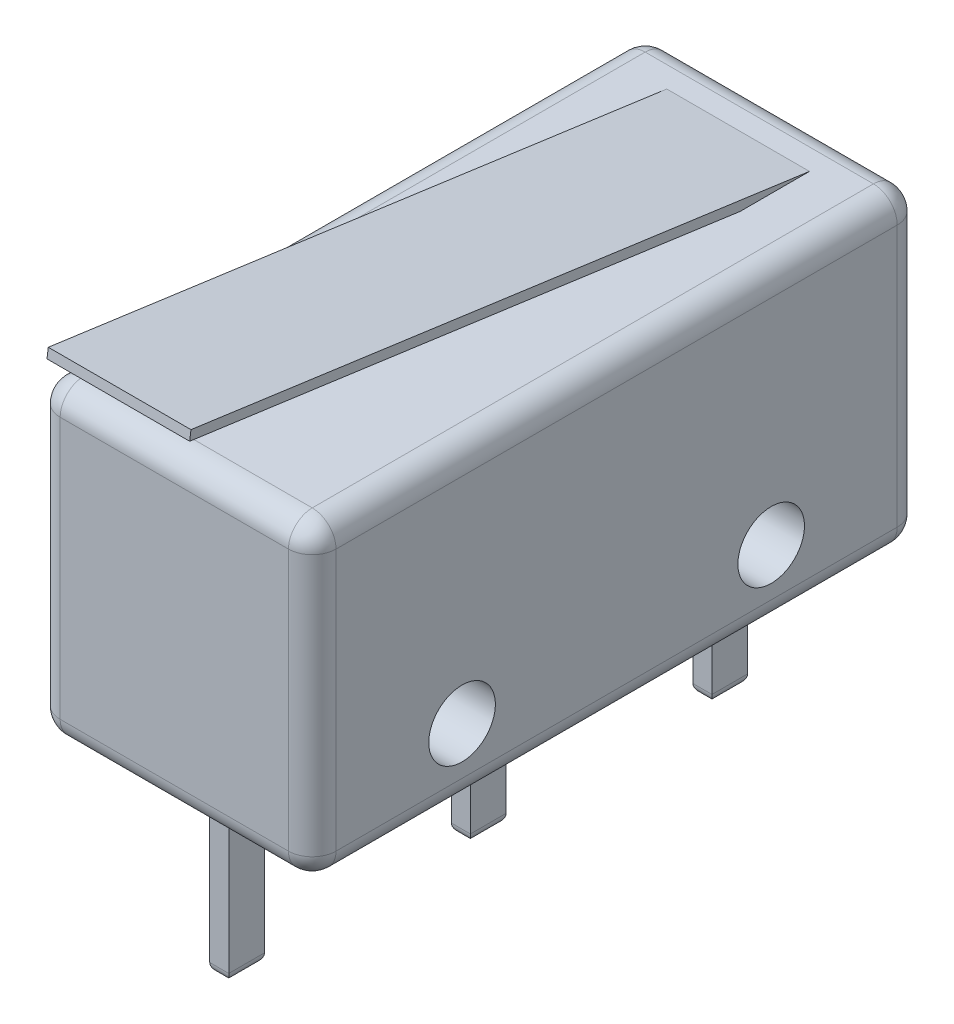
SolidWorks part; units mm, degrees
ref_plane "Front Plane" through (0, 0, 0) normal (0, 0, 1) x (1, 0, 0)
ref_plane "Top Plane" through (0, 0, 0) normal (0, 1, 0) x (1, 0, 0)
ref_plane "Right Plane" through (0, 0, 0) normal (1, 0, 0) x (0, 0, -1)
sketch "Sketch3" plane through (0, 0, 0) normal (1, 0, 0) x (0, 0, -1)
  line L1 (-6.4, 3.25) -> (6.4, 3.25)
  line L2 (-6.4, 3.25) -> (-6.4, -3.25)
  line L3 (-6.4, -3.25) -> (6.4, -3.25)
  line L4 (6.4, 3.25) -> (6.4, -3.25)
  line L5 (-6.4, 3.25) -> (6.4, -3.25) construction
  line L6 (-6.4, -3.25) -> (6.4, 3.25) construction
  point P0 (0, 0)
  dimension "D1" = 6.5
  dimension "D2" = 12.8
extrude "Boss-Extrude1" add sketch "Sketch3" along normal blind 5.8
sketch "Sketch4" plane through (0, -3.25, 0) normal (0, -1, 0) x (1, 0, 0)
  line L0 (3.1, -5.455) -> (3.1, -4.705)
  line L1 (2.7, 0.375) -> (3.1, 0.375)
  line L2 (2.7, 0.375) -> (2.7, -0.375)
  line L3 (2.7, -0.375) -> (3.1, -0.375)
  line L4 (3.1, 0.375) -> (3.1, -0.375)
  line L5 (2.7, 0.375) -> (3.1, -0.375) construction
  line L6 (2.7, -0.375) -> (3.1, 0.375) construction
  line L7 (3.1, -4.705) -> (2.7, -5.455) construction
  line L8 (2.7, -4.705) -> (3.1, -4.705)
  line L9 (0, 0) -> (5.8, 0)
  line L10 (0, 6.4) -> (0, -6.4) construction
  line L11 (5.8, 6.4) -> (5.8, -6.4) construction
  line L12 (2.7, 5.455) -> (2.7, 4.705)
  line L13 (2.7, 5.455) -> (3.1, 5.455)
  line L14 (2.7, 4.705) -> (3.1, 4.705)
  line L15 (3.1, 5.455) -> (3.1, 4.705)
  line L20 (3.1, 4.705) -> (2.7, 5.455) construction
  line L21 (2.7, -5.455) -> (2.7, -4.705)
  line L22 (2.7, -5.455) -> (3.1, -5.455)
  point P0 (2.9, 0)
  point P5 (2.9, 5.08)
  point P18 (2.9, 0)
  dimension "D1" = 0.4
  dimension "D2" = 0.75
  dimension "D3" = 5.08
extrude "Boss-Extrude2" add sketch "Sketch4" along normal blind 3.5 contours L9 L2 L3 L4 | L2 L9 L4 L1 | L15 L13 L12 L14 | L0 L8 L21 L22 region at (2.9, -3.25, 0.1875) region at (2.9, -3.25, -0.1875) region at (2.9, -3.25, 5.08)
fillet "Fillet1" radius 0.2 12 edges at (2.7, -6.75, -5.08) (2.9, -6.75, -4.705) (3.1, -6.75, -5.08) (2.9, -6.75, -5.455) (2.9, -6.75, -0.375) (2.7, -6.75, 0) (2.9, -6.75, 0.375) (3.1, -6.75, 0) (2.9, -6.75, 4.705) (2.7, -6.75, 5.08) (2.9, -6.75, 5.455) (3.1, -6.75, 5.08)
sketch "Sketch5" plane through (0, 0, 0) normal (-1, 0, 0) x (0, 0, 1)
  line L0 (6.4, -3.25) -> (-6.4, -3.25) construction
  line L1 (-3.25, -1.75) -> (3.25, -1.75) construction
  line L3 (-6.4, 3.25) -> (6.4, 3.25) construction
  circle A0 centre (-3.25, -1.75) radius 0.7
  circle A1 centre (3.25, -1.75) radius 0.7
  point P4 (0, -1.75)
  point P9 (0, 3.25)
  dimension "D3" = 1.4
  dimension "D1" = 1.5
  dimension "D2" = 6.5
extrude "Cut-Extrude1" cut sketch "Sketch5" against normal up to next
sketch "Sketch6" plane through (0, 0, 0) normal (-1, 0, 0) x (0, 0, 1)
  line L0 (-5.455, 3.25) -> (7.55, 5.05)
  line L1 (-6.4, 3.25) -> (6.4, 3.25) construction
  line L2 (6.4, -3.25) -> (-6.4, -3.25) construction
  line L3 (-3.9962, 3.25) -> (7.5774, 4.8519)
  line L4 (7.5774, 4.8519) -> (7.55, 5.05)
  line L5 (-5.455, 3.25) -> (-3.9962, 3.25)
  line L6 (-5.4276, 3.0519) -> (7.5774, 4.8519) construction
  circle A0 centre (-3.25, -1.75) radius 0.7 construction
  dimension "D1" = 10.8
  dimension "D2" = 8.3
  dimension "D3" = 0.2
extrude "Boss-Extrude4" add sketch "Sketch6" against normal blind 3 from offset 1.4 offset against normal yes
fillet "Fillet2" radius 0.5 12 edges at (2.9, -3.25, -6.4) (5.8, 0, -6.4) (2.9, 3.25, -6.4) (0, 0, -6.4) (2.9, 3.25, 6.4) (5.8, 0, 6.4) (2.9, -3.25, 6.4) (0, 0, 6.4) (5.8, -3.25, 0) (5.8, 3.25, 0) (0, -3.25, 0) (0, 3.25, 0)
